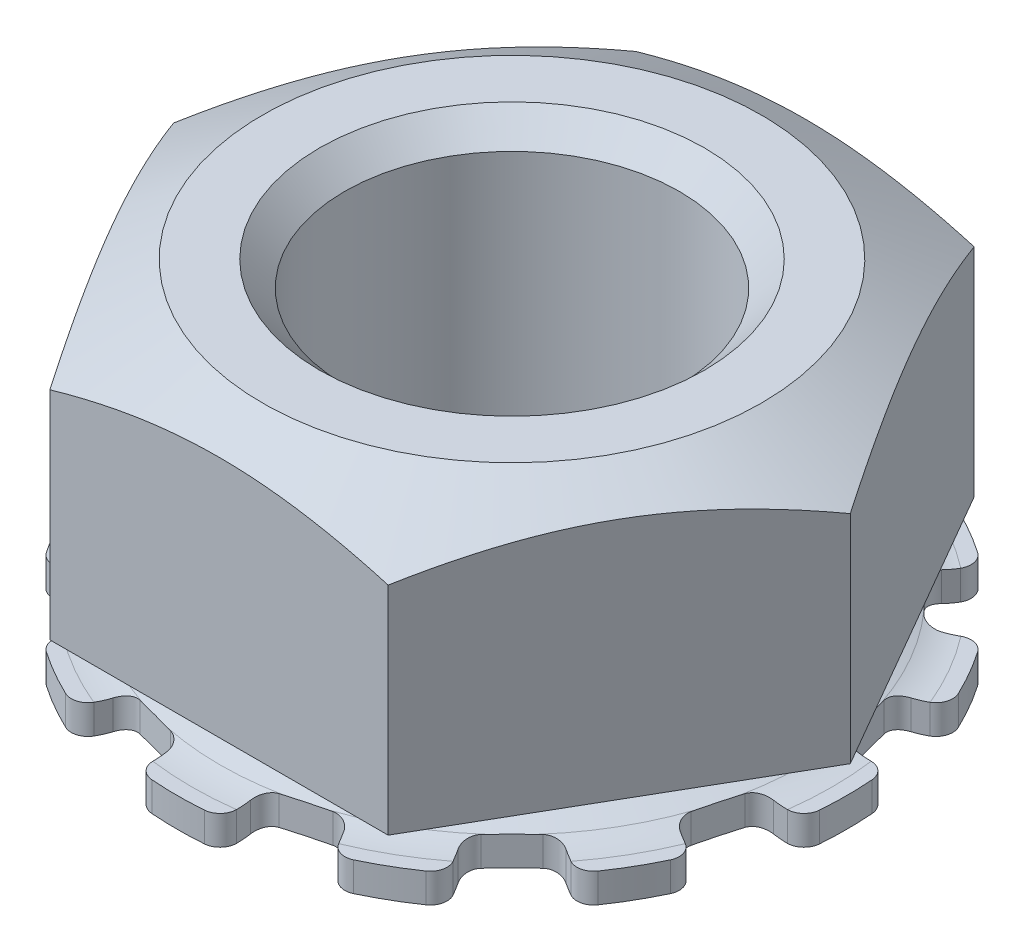
SolidWorks part; units mm, degrees
note: The reader was unsure of these and kept them because the rebuilt part matched: shared geometry of "草图1<3>".
material "铸造碳钢"
ref_plane "前视基准面" through (0, 0, 0) normal (0, 0, 1) x (1, 0, 0)
ref_plane "上视基准面" through (0, 0, 0) normal (0, 1, 0) x (1, 0, 0)
ref_plane "右视基准面" through (0, 0, 0) normal (1, 0, 0) x (0, 0, -1)
sketch "草图1" plane through (0, 0, 0) normal (0, 0, 1) x (1, 0, 0)
  line L0 (0, -97.5064) -> (0, 4777.8117) construction
  line L3 (2, 3.6) -> (2, 0)
  line L4 (2, 0) -> (2.675, 0)
  line L5 (2.675, 0) -> (2.675, 0.35)
  line L6 (2.675, 0.35) -> (2.35, 0.35)
  line L7 (2.35, 0.35) -> (2.35, 0.7)
  line L8 (2.35, 0.7) -> (3.5, 0.7)
  line L9 (3.5, 0.7) -> (3.5, 3.6)
  line L17 (2.35, 0.35) -> (2, 0.35) construction
  line L18 (3.65, 0) -> (4, 0)
  line L19 (3.65, 0.35) -> (4, 0.35)
  line L21 (4, 0.35) -> (4, 0)
  line L22 (2.675, 0) -> (3.65, 0) construction
  line L23 (2.675, 0.35) -> (3.65, 0)
  line L24 (2.675, 0.7) -> (3.65, 0.35)
  line L25 (2.3, 3.9) -> (2.9804, 3.9)
  line L26 (2.9804, 3.9) -> (3.5, 3.6)
  line L27 (2.3, 3.9) -> (2, 3.6)
  dimension "D1" = 45
  dimension "螺纹大径" = 4
  dimension "外齿直径" = 8
  dimension "螺母厚度" = 3.2
  dimension "螺母总厚度" = 3.9
  dimension "D4" = 30
  dimension "倒角" = 0.3
  dimension "底部直径" = 5.35
  dimension "六角对边" = 7
revolve "旋转1" add sketch "草图1" angle 360 about L0
revolve "旋转2" add sketch "草图1<3>" angle 360 about L0
sketch "草图1<3>" plane through (0, 0, 0) normal (0, 0, 1) x (1, 0, 0) same geometry as "草图1"
sketch "草图2" plane through (0, 0.7, 0) normal (0, 1, 0) x (1, 0, 0)
  line L1 (4.0415, 0) -> (2.0207, 3.5)
  line L2 (2.0207, 3.5) -> (-2.0207, 3.5)
  line L3 (-2.0207, 3.5) -> (-4.0415, 0)
  line L4 (-4.0415, 0) -> (-2.0207, -3.5)
  line L5 (-2.0207, -3.5) -> (2.0207, -3.5)
  line L6 (2.0207, -3.5) -> (4.0415, 0)
  circle A0 centre (0, 0) radius 3.5
  circle A4 centre (0, 0) radius 3.5 construction
  circle M11 centre (0, 0) radius 3.5
extrude "凸台-拉伸2" add sketch "草图2" along normal up to surface (2.9 mm away) contours L4 L3 M11 | L5 L4 M11 | L6 L5 M11 | L6 L1 M11 | L2 L1 M11 | L3 L2 M11 up to face at (3.5, 3.6, 0)
fillet "圆角1" radius 1 2 edges at (3.65, 0, 0) (3.65, 0.35, 0)
sketch "草图3" plane through (0, 0, 0) normal (0, 1, 0) x (1, 0, 0)
  line L3 (-0.5, 3.9686) -> (-0.5, 3.4686)
  line L4 (-0.5, 3.4686) -> (0.5, 3.4686) construction
  line L5 (0.5, 3.4686) -> (0.5, 3.9686)
  line L6 (0, 0) -> (0, 3.4686) construction
  line L7 (0.9007, 3.3613) -> (1.0353, 3.8637)
  line L8 (-0.9007, 3.3613) -> (-1.0353, 3.8637)
  line L9 (-0.5, 3.4686) -> (-0.9007, 3.3613)
  line L10 (0.5, 3.4686) -> (0.9007, 3.3613)
  line L11 (0.9007, 3.3613) -> (0, 0) construction
  line L12 (0, 0) -> (-0.9007, 3.3613) construction
  arc A2 (-0.5, 3.9686) -> (-1.0353, 3.8637) centre (0, 0) ccw
  circle A3 centre (0, 0) radius 4 construction
  arc A4 (1.0353, 3.8637) -> (0.5, 3.9686) centre (0, 0) ccw
  dimension "D2" = 30
  dimension "齿宽" = 1
  dimension "齿高" = 0.5
extrude "切除-拉伸1" cut sketch "草图3" along normal up to next
pattern_circular "阵列(圆周)1" count 12 over 360 about axis through (0, 0, 0) along (0, 1, 0) of "切除-拉伸1"
fillet "圆角2" radius 0.2 168 edges at (-0.5, 0, -3.8799) (-0.5, 0.35, -3.8799) (-0.5, 0.2274, -3.4686) (-0.5, 0.175, -3.9686) (0.5, 0.2274, -3.4686) (0.5, 0.35, -3.8799) (0.5, 0.175, -3.9686) (0.5, 0, -3.8799) (2.373, 0, 3.1101) (2.373, 0.35, 3.1101) (2.1673, 0.2274, 2.7539) (2.7539, 0.2274, 2.1673) (2.4173, 0.175, 3.1869) (3.1101, 0.35, 2.373) (3.1869, 0.175, 2.4173) (3.1101, 0, 2.373) (0.5, 1.9857, 3.9611) (0.5, 0, 3.8799) (0.5, 0.35, 3.8799) (0.5, 2.3357, 3.9611) (0.5, 0.2274, 3.4686) (1.3013, 0.2274, 3.2539) (0.5, 0.175, 3.9686) (1.5069, 0.35, 3.6101) (1.5513, 0.175, 3.6869) (1.5069, 0, 3.6101) (3.9611, 1.9857, -0.5) (3.8799, 0, -0.5) (3.8799, 0.35, -0.5) (3.9611, 2.3357, -0.5) (3.4686, 0.2274, -0.5) (3.2539, 0.2274, -1.3013) (3.9686, 0.175, -0.5) (3.6101, 0.35, -1.5069) (3.6869, 0.175, -1.5513) (3.6101, 0, -1.5069) (3.6101, 0, 1.5069) (3.6101, 0.35, 1.5069) (3.2539, 0.2274, 1.3013) (3.4686, 0.2274, 0.5) (3.6869, 0.175, 1.5513) (3.833, 2.3491, 0.5) (3.8799, 0.35, 0.5) (3.9686, 0.175, 0.5) (3.8799, 0, 0.5) (-3.8799, 0, 0.5) (-3.8799, 0.35, 0.5) (-3.4686, 0.2274, 0.5) (-3.2539, 0.2274, 1.3013) (-3.9686, 0.175, 0.5) (-3.6101, 0.35, 1.5069) (-3.6869, 0.175, 1.5513) (-3.6101, 0, 1.5069) (-3.6101, 0, -1.5069) (-3.6101, 0.35, -1.5069) (-3.2539, 0.2274, -1.3013) (-3.4686, 0.2274, -0.5) (-3.6869, 0.175, -1.5513) (-3.8799, 0.35, -0.5) (-3.9686, 0.175, -0.5) (-3.8799, 0, -0.5) (-1.3013, 0.2274, -3.2539) (-1.5069, 0.35, -3.6101) (-1.5513, 0.175, -3.6869) (-1.5069, 0, -3.6101) (-1.5069, 0, 3.6101) (-1.5069, 0.35, 3.6101) (-1.3013, 0.2274, 3.2539) (-0.5, 0.2274, 3.4686) (-1.5513, 0.175, 3.6869) (-0.5, 0.35, 3.8799) (-0.5, 0.175, 3.9686) (-0.5, 0, 3.8799) (-3.1101, 0, 2.373) (-3.1101, 0.35, 2.373) (-2.7539, 0.2274, 2.1673) (-2.1673, 0.2274, 2.7539) (-3.1869, 0.175, 2.4173) (-2.373, 0.35, 3.1101) (-2.4173, 0.175, 3.1869) (-2.373, 0, 3.1101) (3.1101, 0, -2.373) (3.1101, 0.35, -2.373) (2.7539, 0.2274, -2.1673) (2.1673, 0.2274, -2.7539) (3.1869, 0.175, -2.4173) (2.373, 0.35, -3.1101) (2.4173, 0.175, -3.1869) (2.373, 0, -3.1101) (1.5069, 0, -3.6101) (1.5069, 0.35, -3.6101) (1.3013, 0.2274, -3.2539) (1.5513, 0.175, -3.6869) (-2.373, 0, -3.1101) (-2.373, 0.35, -3.1101) (-2.1673, 0.2274, -2.7539) (-2.7539, 0.2274, -2.1673) (-2.4173, 0.175, -3.1869) (-3.1101, 0.35, -2.373) (-3.1869, 0.175, -2.4173) (-3.1101, 0, -2.373)
other "冻结***"
